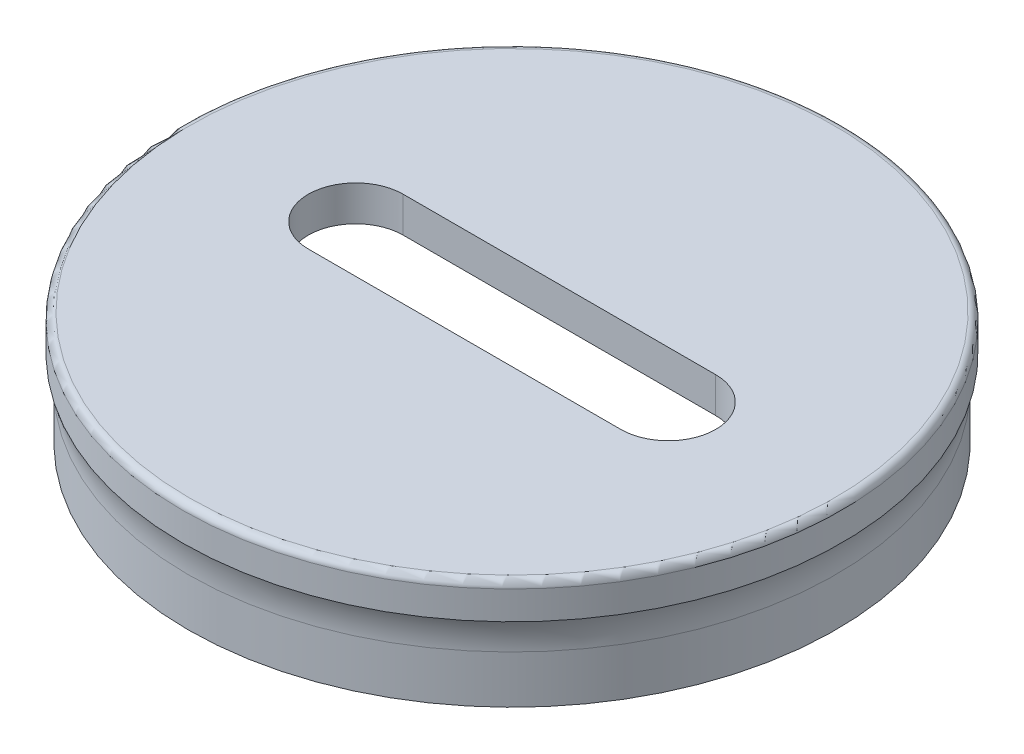
SolidWorks part; units mm, degrees
material "Polylactic Acid"
ref_plane "Front Plane" through (0, 0, 0) normal (0, 0, 1) x (1, 0, 0)
ref_plane "Top Plane" through (0, 0, 0) normal (0, 1, 0) x (1, 0, 0)
ref_plane "Right Plane" through (0, 0, 0) normal (1, 0, 0) x (0, 0, -1)
sketch "Sketch1" plane through (0, 0, 0) normal (0, 1, 0) x (1, 0, 0)
  circle A0 centre (0, 0) radius 57.023
  circle A1 centre (0, 0) radius 58.05
  dimension "D1" = 114.046
  dimension "D2" = 116.1
extrude "Boss-Extrude1" add sketch "Sketch1" along normal blind 13.97
sketch "Sketch2" plane through (0, 13.97, 0) normal (0, 1, 0) x (1, 0, 0)
  circle A0 centre (0, 0) radius 59.055
  dimension "D1" = 118.11
extrude "Boss-Extrude2" add sketch "Sketch2" along normal blind 6.35
thread "Thread1" pitch 3.175 method extrude profile "Thread Profile3" start angle 1, offset 0, length 0, pitch 3.175, diameter 114.046
ref_plane "Plane3" through (-57.0143, 13.97, -0.9952) normal (-0.0175, 0, 0.9998) x (-0.9998, 0, -0.0175)
sketch "Thread Profile3" plane through (-57.0143, 13.97, -0.9952) normal (-0.0175, 0, 0.9998) x (-0.9998, 0, -0.0175)
  line L0 (0, 0) -> (0, 3.175) construction
  line L11 (0, 0) -> (0, 2.7781)
  line L12 (0, 2.7781) -> (-1.7185, 1.7859)
  line L13 (-1.7185, 1.7859) -> (-1.7185, 0.9922)
  line L15 (-1.7185, 0.9922) -> (0, 0)
  line L17 (-1.7185, 1.3891) -> (0, 1.3891) construction
  point P2 (0, 0)
  dimension "Pitch" = 3.175
  dimension "Profile_Angle" = 60
  dimension "Profile_Land" = 0.7937
  dimension "Profile_Height" = 1.7185
fillet "Fillet1" radius 1.27 1 edges at (0, 20.32, 59.055)
fillet "Fillet2" radius 15 1 edges at (0, 13.97, 58.05)
sketch "Sketch3" plane through (0, 20.32, 0) normal (0, 1, 0) x (1, 0, 0)
  line L0 (0, 0) -> (-57.785, 0)
  line L1 (-28, 8.5) -> (28, 8.5)
  line L2 (-28, 8.5) -> (-28, -8.5)
  line L3 (-28, -8.5) -> (28, -8.5)
  line L4 (28, 8.5) -> (28, -8.5)
  line L5 (0, 0) -> (0, 57.785)
  circle A0 centre (0, 0) radius 57.785 construction
  arc A1 (-28, 8.5) -> (-28, -8.5) centre (-28, 0) ccw
  arc A2 (28, 8.5) -> (28, -8.5) centre (28, 0) cw
  dimension "D1" = 17
  dimension "D2" = 56
  dimension "D3" = 28
  dimension "D4" = 8.5
extrude "Cut-Extrude1" cut sketch "Sketch3" against normal blind 10 contours L2 A1 L0 | L0 L5 L1 L2 | L0 A1 L2 | L5 L0 L2 L3 L4 L1 | A2 L4 region at (4.6667, 20.32, 1.4167) region at (-14, 20.32, -4.25) region at (-31.6075, 20.32, 3.6075) region at (-31.6075, 20.32, -3.6075) region at (31.6075, 20.32, 0)
